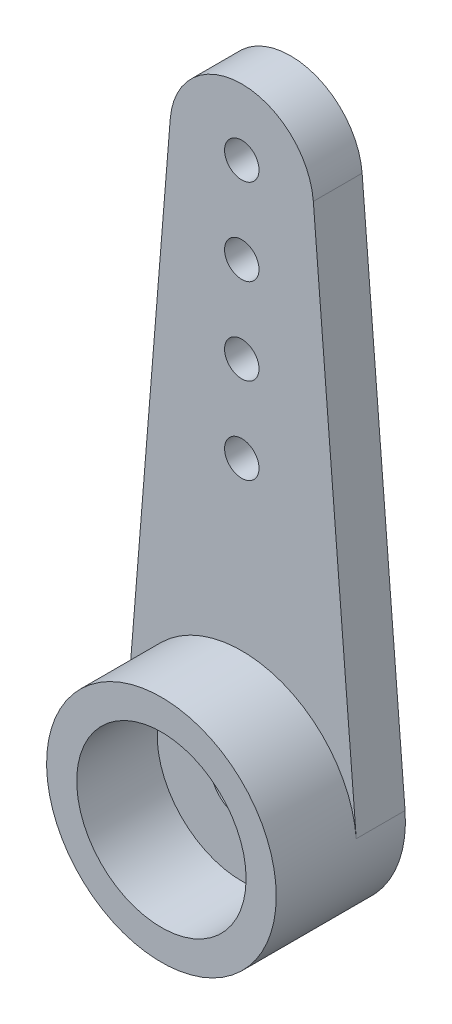
SolidWorks part; units mm, degrees
ref_plane "Спереди" through (0, 0, 0) normal (0, 0, 1) x (1, 0, 0)
ref_plane "Сверху" through (0, 0, 0) normal (0, 1, 0) x (1, 0, 0)
ref_plane "Справа" through (0, 0, 0) normal (1, 0, 0) x (0, 0, -1)
sketch "Эскиз1" plane through (0, 0, 0) normal (0, 0, 1) x (1, 0, 0)
  circle A0 centre (0, 0) radius 4
  circle A1 centre (0, 0) radius 2.5
  circle A2 centre (0, 0) radius 1.1
  circle A3 centre (0, 0) radius 2.95
  dimension "D1" = 8
  dimension "D2" = 5
  dimension "D3" = 2.2
  dimension "D4" = 5.9
extrude "Бобышка-Вытянуть1" add sketch "Эскиз1" along normal blind 4.5 contours A0 A3 region at (-3.8869, 0, 0)
extrude "Бобышка-Вытянуть2" add sketch "Эскиз1<3>" along normal blind 1.7 contours A3 A1 | A1 A2 region at (-2.4293, 0, 0) region at (-2.8666, 0, 0)
sketch "Эскиз1<3>" plane through (0, 0, 0) normal (0, 0, 1) x (1, 0, 0) same geometry as "Эскиз1"
extrude "Вырез-Вытянуть1" cut sketch "Эскиз1<4>" along normal blind 0.4 contours A3 A1 | A1 A2 region at (-2.4293, 0, 0) region at (-2.8666, 0, 0)
sketch "Эскиз1<4>" plane through (0, 0, 0) normal (0, 0, 1) x (1, 0, 0) same geometry as "Эскиз1"
sketch "Эскиз2" plane through (0, 0, 0) normal (0, 0, 1) x (1, 0, 0)
  line L0 (0, 0) -> (0, 27.4115) construction
  line L1 (-2.4919, 18.8016) -> (-3.987, 0.3226)
  line L2 (2.4919, 18.8016) -> (3.987, 0.3226)
  line L3 (-7.4124, 21.1) -> (12.2553, 21.1) construction
  line L4 (-2.4919, 18.8016) -> (2.4919, 18.8016) construction
  circle A0 centre (0, 0) radius 4 construction
  circle A1 centre (0, 0) radius 4
  arc A2 (-2.4919, 18.8016) -> (2.4919, 18.8016) centre (0, 18.6) cw
  circle A3 centre (0, 18.8016) radius 0.6
  circle A4 centre (0, 15.8016) radius 0.6
  circle A5 centre (0, 12.8016) radius 0.6
  circle A6 centre (0, 9.8016) radius 0.6
  point P9 (0, 49.6)
  point P20 (0, 0)
  point P21 (0, 15.8566)
  point P22 (0, 13.0659)
  point P23 (0, 10.2576)
  dimension "D1" = 2.5
  dimension "D3" = 1.2
  dimension "D2" = 17.1
  dimension "D4" = 1.8
  dimension "D5" = 1.8
  dimension "D6" = 1.8
extrude "Бобышка-Вытянуть3" add sketch "Эскиз2" along normal blind 1.7 contours A2 L1 A1 L2 A6 A5 A4 A3 region at (0, 11.1079, 0)
equation "\"D1@Бобышка-Вытянуть2\"=4.5-2.8"
equation "\"D4@Эскиз2\"=4.2-2.4"
equation "\"D5@Эскиз2\"=\"D4@Эскиз2\""
equation "\"D6@Эскиз2\"=\"D5@Эскиз2\""
